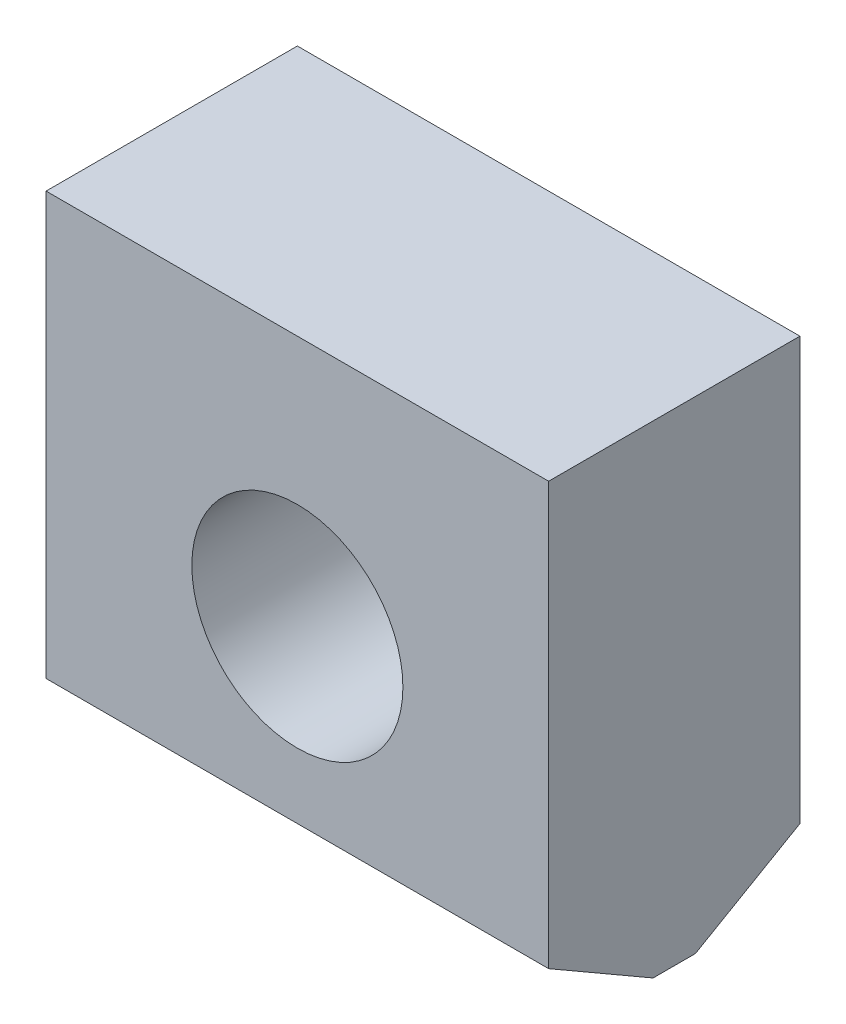
SolidWorks part; units mm, degrees
material "Простая углеродистая сталь"
ref_plane "Спереди" through (0, 0, 0) normal (0, 0, 1) x (1, 0, 0)
ref_plane "Сверху" through (0, 0, 0) normal (0, 1, 0) x (1, 0, 0)
ref_plane "Справа" through (0, 0, 0) normal (1, 0, 0) x (0, 0, -1)
sketch "Эскиз1" plane through (0, 0, 0) normal (0, 0, 1) x (1, 0, 0)
  line L1 (0, 0) -> (50, 0)
  line L2 (0, 0) -> (0, 48)
  line L3 (0, 48) -> (50, 48)
  line L4 (50, 0) -> (50, 48)
  point P5 (25, 48)
  dimension "D1" = 48
  dimension "D2" = 50
extrude "Бобышка-Вытянуть1" add sketch "Эскиз1" along normal blind 25
sketch "Эскиз2" plane through (0, 0, 25) normal (0, 0, 1) x (1, 0, 0)
  line L0 (0, 0) -> (50, 0) construction
  line L1 (50, 0) -> (50, 48) construction
  circle A0 centre (25, 23) radius 10.5
  dimension "D2" = 23
  dimension "D3" = 25
  dimension "D4" = 21
extrude "Вырез-Вытянуть1" cut sketch "Эскиз2" against normal through all
chamfer "Фаска1" distance 6 angle 60 1 edges at (25, 0, 0) first distance on face at (35.5, 23, 0)
chamfer "Фаска2" distance 6 angle 60 1 edges at (25, 0, 25) first distance on face at (35.5, 23, 25)
